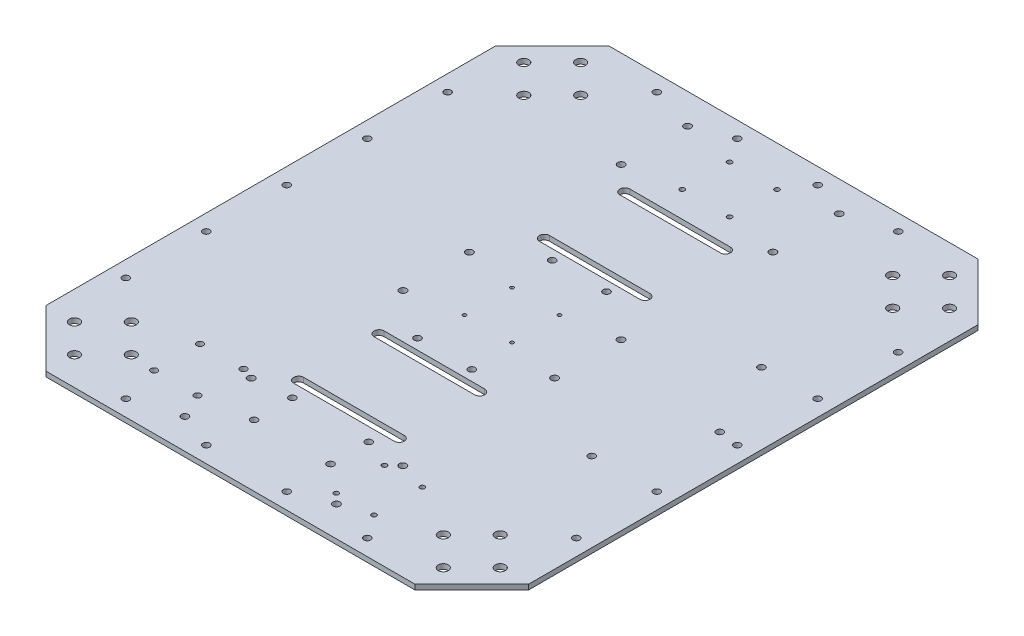
SolidWorks part; units mm, degrees
ref_plane "Front Plane" through (0, 0, 0) normal (0, 0, 1) x (1, 0, 0)
ref_plane "Top Plane" through (0, 0, 0) normal (0, 1, 0) x (1, 0, 0)
ref_plane "Right Plane" through (0, 0, 0) normal (1, 0, 0) x (0, 0, -1)
sketch "Sketch1" plane through (0, 0, 0) normal (0, 1, 0) x (1, 0, 0)
  line L0 (-121.2861, 87.138) -> (-85.365, 123.059)
  line L1 (-121.2861, 123.059) -> (183.5139, 123.059)
  line L2 (-121.2861, 123.059) -> (-121.2861, -232.541)
  line L3 (-121.2861, -232.541) -> (183.5139, -232.541)
  line L4 (183.5139, 123.059) -> (183.5139, -232.541)
  line L5 (31.1139, 95.069) -> (31.1139, -294.9418) construction
  line L6 (-146.0448, -54.741) -> (218.038, -54.741) construction
  line L7 (183.5139, 87.138) -> (147.5929, 123.059)
  line L8 (183.5139, -196.62) -> (147.5929, -232.541)
  line L9 (-121.2861, -196.62) -> (-85.365, -232.541)
  circle A0 centre (-16.7651, 104.009) radius 2.2225
  circle A1 centre (78.9929, 104.009) radius 2.2225
  circle A2 centre (-16.7651, 62.099) radius 2.2225
  circle A3 centre (78.9929, 62.099) radius 2.2225
  circle A4 centre (-16.7651, -171.581) radius 2.2225
  circle A5 centre (78.9929, -171.581) radius 2.2225
  circle A6 centre (78.9929, -213.491) radius 2.2225
  circle A7 centre (-16.7651, -213.491) radius 2.2225
  circle A8 centre (-16.7651, -33.786) radius 2.2225
  circle A9 centre (78.9929, -33.786) radius 2.2225
  circle A10 centre (78.9929, -75.696) radius 2.2225
  circle A11 centre (-16.7651, -75.696) radius 2.2225
  point P8 (31.1139, 123.059)
  point P11 (-121.2861, -54.741)
  dimension "D6" = 95.758
  dimension "D13" = 4.445
  dimension "D1" = 304.8
  dimension "D2" = 355.6
  dimension "D3" = 45
  dimension "D4" = 50.8
  dimension "D5" = 41.91
  dimension "D7" = 104.521
  dimension "D8" = 19.05
  dimension "D9" = 41.91
  dimension "D10" = 20.955
  dimension "D11" = 95.758
  dimension "D12" = 47.879
extrude "Boss-Extrude1" add sketch "Sketch1" along normal blind 3.175 contours L2 L9 L3 L8 L4 L7 L1 L0 region at (31.1139, 0, 54.741)
sketch "Sketch2" plane through (0, 3.175, 0) normal (0, 1, 0) x (1, 0, 0)
  line L0 (31.1139, 123.059) -> (31.1139, -287.8465) construction
  line L1 (-85.365, 123.059) -> (147.5929, 123.059) construction
  line L2 (183.5139, -54.741) -> (-158.2106, -54.741) construction
  line L3 (183.5139, 87.138) -> (183.5139, -196.62) construction
  circle A0 centre (13.8419, -12.069) radius 2.159
  circle A1 centre (48.1319, -12.069) radius 2.159
  circle A2 centre (13.8419, -97.159) radius 2.159
  circle A3 centre (48.1319, -97.159) radius 2.159
  dimension "D5" = 4.318
  dimension "D6" = 4.318
  dimension "D7" = 4.318
  dimension "D8" = 4.318
  dimension "D1" = 17.272
  dimension "D2" = 34.29
  dimension "D3" = 85.09
  dimension "D4" = 42.672
extrude "Cut-Extrude1" cut sketch "Sketch2" against normal through all
sketch "Sketch4" plane through (0, 3.175, 0) normal (0, 1, 0) x (1, 0, 0)
  line L0 (-0.6361, 48.256) -> (62.8639, 48.256) construction
  line L1 (-0.6361, 51.431) -> (62.8639, 51.431)
  line L2 (-0.6361, 45.081) -> (62.8639, 45.081)
  line L3 (-0.6361, -2.544) -> (62.8639, -2.544) construction
  line L4 (-0.6361, 0.631) -> (62.8639, 0.631)
  line L5 (-0.6361, -5.719) -> (62.8639, -5.719)
  line L6 (31.1139, 123.059) -> (31.1139, -75.2432) construction
  line L7 (-85.365, 123.059) -> (147.5929, 123.059) construction
  line L8 (-121.2861, -54.741) -> (257.7387, -54.741) construction
  line L9 (-121.2861, 87.138) -> (-121.2861, -196.62) construction
  line L10 (31.1139, -232.541) -> (31.1139, -34.2388) construction
  line L11 (-0.6361, -106.938) -> (62.8639, -106.938) construction
  line L12 (-0.6361, -110.113) -> (62.8639, -110.113)
  line L13 (-0.6361, -103.763) -> (62.8639, -103.763)
  line L14 (-0.6361, -157.738) -> (62.8639, -157.738) construction
  line L15 (-0.6361, -160.913) -> (62.8639, -160.913)
  line L16 (-0.6361, -154.563) -> (62.8639, -154.563)
  arc A0 (-0.6361, 51.431) -> (-0.6361, 45.081) centre (-0.6361, 48.256) ccw
  arc A1 (62.8639, 45.081) -> (62.8639, 51.431) centre (62.8639, 48.256) ccw
  arc A2 (-0.6361, 0.631) -> (-0.6361, -5.719) centre (-0.6361, -2.544) ccw
  arc A3 (62.8639, -5.719) -> (62.8639, 0.631) centre (62.8639, -2.544) ccw
  circle A4 centre (48.1319, -12.069) radius 2.159 construction
  arc A5 (-0.6361, -110.113) -> (-0.6361, -103.763) centre (-0.6361, -106.938) cw
  arc A6 (62.8639, -103.763) -> (62.8639, -110.113) centre (62.8639, -106.938) cw
  arc A7 (-0.6361, -160.913) -> (-0.6361, -154.563) centre (-0.6361, -157.738) cw
  arc A8 (62.8639, -154.563) -> (62.8639, -160.913) centre (62.8639, -157.738) cw
  point P2 (31.1139, 48.256)
  point P7 (31.1139, -2.544)
  point P28 (31.1139, -106.938)
  point P35 (31.1139, -157.738)
  dimension "D1" = 63.5
  dimension "D2" = 63.5
  dimension "D3" = 6.35
  dimension "D4" = 6.35
  dimension "D5" = 44.45
  dimension "D6" = 6.35
extrude "Cut-Extrude2" cut sketch "Sketch4" against normal through all
sketch "Sketch7" plane through (0, 3.175, 0) normal (0, 1, 0) x (1, 0, 0)
  line L0 (31.1139, 123.059) -> (31.1139, -19.2461) construction
  line L3 (-85.365, 123.059) -> (147.5929, 123.059) construction
  circle A0 centre (16.1279, 67.687) radius 1.524
  circle A1 centre (46.0999, 67.687) radius 1.524
  circle A2 centre (16.1279, 97.659) radius 1.524
  circle A3 centre (46.0999, 97.659) radius 1.524
  dimension "D1" = 3.048
  dimension "D2" = 3.048
  dimension "D4" = 14.986
  dimension "D3" = 29.972
  dimension "D5" = 25.4
extrude "Cut-Extrude3" cut sketch "Sketch7" against normal through all
sketch "Sketch8" plane through (0, 3.175, 0) normal (0, 1, 0) x (1, 0, 0)
  line L0 (-85.365, -232.541) -> (147.5929, -232.541) construction
  line L1 (183.5139, 87.138) -> (183.5139, -196.62) construction
  circle A0 centre (73.0239, -207.649) radius 1.524
  circle A1 centre (73.0239, -177.169) radius 1.524
  circle A2 centre (96.8999, -207.649) radius 1.524
  circle A3 centre (96.8999, -177.169) radius 1.524
  dimension "D1" = 3.048
  dimension "D2" = 30.48
  dimension "D3" = 23.876
  dimension "D4" = 24.892
  dimension "D5" = 86.614
extrude "Cut-Extrude4" cut sketch "Sketch8" against normal through all and the other way through all
sketch "Sketch9" plane through (0, 0, 0) normal (0, -1, 0) x (-1, 0, 0)
  line L0 (85.365, -232.541) -> (-147.5929, -232.541) construction
  line L1 (121.2861, 87.138) -> (121.2861, -196.62) construction
  circle A0 centre (51.6494, -197.9691) radius 2.032
  circle A1 centre (24.2174, -197.9691) radius 2.032
  circle A2 centre (51.6494, -169.0131) radius 2.032
  circle A3 centre (24.2174, -169.0131) radius 2.032
  dimension "D1" = 4.064
  dimension "D2" = 27.432
  dimension "D3" = 28.956
  dimension "D4" = 34.5719
  dimension "D5" = 69.6366
extrude "Cut-Extrude5" cut sketch "Sketch9" against normal through all
sketch "Sketch10" plane through (0, 0, 0) normal (0, -1, 0) x (1, 0, 0)
  line L0 (-85.365, 232.541) -> (147.5929, 232.541) construction
  line L1 (31.1139, 232.541) -> (31.1139, 128.7119) construction
  circle A0 centre (6.9839, 193.4758) radius 2.159
  circle A1 centre (55.2439, 193.4758) radius 2.159
  circle A2 centre (6.9839, 169.3458) radius 2.159
  circle A3 centre (55.2439, 169.3458) radius 2.159
  dimension "D1" = 4.318
  dimension "D2" = 48.26
  dimension "D4" = 39.0652
  dimension "D6" = 4.318
  dimension "D7" = 4.318
  dimension "D8" = 4.318
  dimension "D3" = 24.13
  dimension "D5" = 24.13
extrude "Cut-Extrude6" cut sketch "Sketch10" against normal through all
sketch "Sketch13" plane through (0, 0, 0) normal (0, -1, 0) x (1, 0, 0)
  line L0 (31.1139, -123.059) -> (31.1139, 261.4711) construction
  line L1 (-85.365, -123.059) -> (147.5929, -123.059) construction
  line L2 (-121.2861, 54.741) -> (239.2508, 54.741) construction
  line L3 (-121.2861, -87.138) -> (-121.2861, 196.62) construction
  circle A0 centre (16.1139, 69.741) radius 1.1
  circle A1 centre (16.1139, 39.741) radius 1.1
  circle A2 centre (46.1139, 39.741) radius 1.1
  circle A3 centre (46.1139, 69.741) radius 1.1
  dimension "D1" = 2.2
  dimension "D2" = 2.2
  dimension "D3" = 30
  dimension "D4" = 15
  dimension "D5" = 15
extrude "Cut-Extrude8" cut sketch "Sketch13" against normal through all
sketch "Sketch14" plane through (0, 0, 0) normal (0, -1, 0) x (1, 0, 0)
  line L0 (31.1139, 232.541) -> (31.1139, -154.5354) construction
  line L1 (-85.365, 232.541) -> (147.5929, 232.541) construction
  line L2 (-121.2861, 54.741) -> (331.9066, 54.741) construction
  line L3 (-121.2861, -87.138) -> (-121.2861, 196.62) construction
  line L4 (-85.365, 214.5805) -> (-103.3255, 196.62) construction
  line L5 (-103.3255, 196.62) -> (-85.365, 178.6595) construction
  line L6 (-85.365, 178.6595) -> (-67.4045, 196.62) construction
  line L7 (-67.4045, 196.62) -> (-85.365, 214.5805) construction
  line L8 (-121.2861, 196.62) -> (-85.365, 232.541) construction
  line L9 (-103.3255, 214.5805) -> (-48.3665, 159.6215) construction
  circle A0 centre (-103.3255, 196.62) radius 3.175
  circle A1 centre (-85.365, 214.5805) radius 3.175
  circle A2 centre (-85.365, 178.6595) radius 3.175
  circle A3 centre (-67.4045, 196.62) radius 3.175
  circle A4 centre (129.6324, 196.62) radius 3.175
  circle A5 centre (147.5929, 178.6595) radius 3.175
  circle A6 centre (165.5534, 196.62) radius 3.175
  circle A7 centre (147.5929, 214.5805) radius 3.175
  circle A8 centre (-85.365, -105.0985) radius 3.175
  circle A9 centre (-103.3255, -87.138) radius 3.175
  circle A10 centre (-85.365, -69.1774) radius 3.175
  circle A11 centre (-67.4045, -87.138) radius 3.175
  circle A12 centre (165.5534, -87.138) radius 3.175
  circle A13 centre (147.5929, -69.1774) radius 3.175
  circle A14 centre (147.5929, -105.0985) radius 3.175
  circle A15 centre (129.6324, -87.138) radius 3.175
  dimension "D3" = 6.35
  dimension "D4" = 6.35
  dimension "D5" = 6.35
  dimension "D6" = 6.35
  dimension "D2" = 12.7
  dimension "D7" = 90
  dimension "D8" = 25.4
  dimension "D9" = 25.4
  dimension "D10" = 12.7
  dimension "D11" = 90
extrude "Cut-Extrude9" cut sketch "Sketch14" against normal through all
sketch "Sketch15" plane through (0, 0, 0) normal (0, -1, 0) x (1, 0, 0)
  line L0 (31.1139, 232.541) -> (31.1139, 125.875) construction
  line L1 (-85.365, 232.541) -> (147.5929, 232.541) construction
  line L2 (-121.2861, 54.741) -> (75.4631, 54.741) construction
  line L3 (-121.2861, -87.138) -> (-121.2861, 196.62) construction
  circle A0 centre (5.7139, 222.381) radius 2.159
  circle A1 centre (-45.0861, 222.381) radius 2.159
  circle A2 centre (-111.1261, 54.741) radius 2.159
  circle A3 centre (-111.1261, 105.541) radius 2.159
  circle A4 centre (-111.1261, 156.341) radius 2.159
  circle A5 centre (173.3539, 156.341) radius 2.159
  circle A6 centre (173.3539, 105.541) radius 2.159
  circle A7 centre (173.3539, 54.741) radius 2.159
  circle A8 centre (107.3139, 222.381) radius 2.159
  circle A9 centre (56.5139, 222.381) radius 2.159
  circle A10 centre (56.5139, -112.899) radius 2.159
  circle A11 centre (107.3139, -112.899) radius 2.159
  circle A12 centre (173.3539, 3.941) radius 2.159
  circle A13 centre (173.3539, -46.859) radius 2.159
  circle A14 centre (-111.1261, -46.859) radius 2.159
  circle A15 centre (-111.1261, 3.941) radius 2.159
  circle A16 centre (-45.0861, -112.899) radius 2.159
  circle A17 centre (5.7139, -112.899) radius 2.159
  dimension "D3" = 4.318
  dimension "D4" = 4.318
  dimension "D8" = 4.318
  dimension "D9" = 4.318
  dimension "D10" = 4.318
  dimension "D1" = 25.4
  dimension "D2" = 50.8
  dimension "D5" = 10.16
  dimension "D6" = 50.8
  dimension "D7" = 50.8
  dimension "D11" = 10.16
extrude "Cut-Extrude10" cut sketch "Sketch15" against normal through all
sketch "Sketch16" plane through (0, 0, 0) normal (0, -1, 0) x (-1, 0, 0)
  line L1 (-103.7737, -99.6794) -> (-153.6537, -99.6794)
  line L2 (-103.7737, -99.6794) -> (-103.7737, -11.5294)
  line L3 (-103.7737, -11.5294) -> (-153.6537, -11.5294)
  line L4 (-153.6537, -99.6794) -> (-153.6537, -11.5294)
  line L5 (-183.5139, 87.138) -> (-183.5139, -196.62) construction
  circle A0 centre (-133.3337, -106.6794) radius 2.159
  circle A1 centre (-138.4137, -4.5294) radius 2.159
  circle A2 centre (-160.6539, -53.0294) radius 2.159
  dimension "D3" = 7
  dimension "D4" = 7.0002
  dimension "D5" = 7
  dimension "D6" = 20.32
  dimension "D7" = 15.24
  dimension "D8" = 46.65
  dimension "D9" = 4.318
  dimension "D10" = 4.318
  dimension "D11" = 4.318
  dimension "D1" = 88.15
  dimension "D2" = 49.88
  dimension "D12" = 22.86
extrude "Cut-Extrude11" cut sketch "Sketch16" against normal through all contours A2 | A0 | A1
